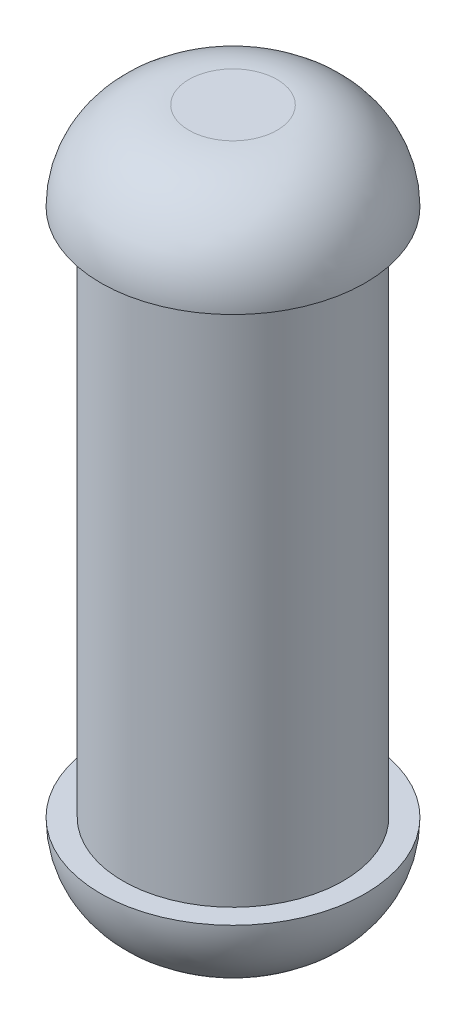
SolidWorks part; units mm, degrees
ref_plane "Front Plane" through (0, 0, 0) normal (0, 0, 1) x (1, 0, 0)
ref_plane "Top Plane" through (0, 0, 0) normal (0, 1, 0) x (1, 0, 0)
ref_plane "Right Plane" through (0, 0, 0) normal (1, 0, 0) x (0, 0, -1)
sketch "Sketch1" plane through (0, 0, 0) normal (0, 1, 0) x (1, 0, 0)
  circle A0 centre (0, 0) radius 3
extrude "Boss-Extrude1" add sketch "Sketch1" along normal blind 2
sketch "Sketch2" plane through (0, 0, 0) normal (0, -1, 0) x (1, 0, 0)
  circle A0 centre (0, 0) radius 2.5
extrude "Boss-Extrude2" add sketch "Sketch2" along normal blind 12
sketch "Sketch3" plane through (0, -12, 0) normal (0, -1, 0) x (1, 0, 0)
  circle A0 centre (0, 0) radius 3
extrude "Boss-Extrude3" add sketch "Sketch3" along normal blind 2
fillet "Fillet1" radius 2 2 edges at (0, 2, 3) (0, -14, -3)
